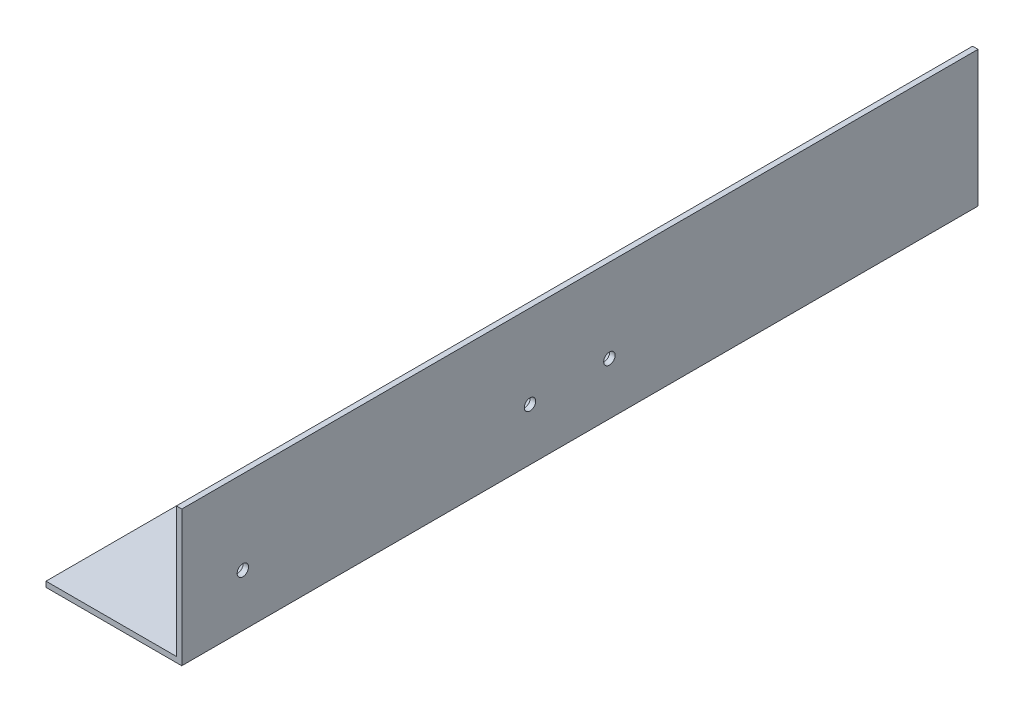
SolidWorks part; units mm, degrees
ref_plane "Front Plane" through (0, 0, 0) normal (0, 0, 1) x (1, 0, 0)
ref_plane "Top Plane" through (0, 0, 0) normal (0, 1, 0) x (1, 0, 0)
ref_plane "Right Plane" through (0, 0, 0) normal (1, 0, 0) x (0, 0, -1)
sketch "Sketch1" plane through (0, 0, 0) normal (0, 0, 1) x (1, 0, 0)
  line L0 (0, 0) -> (-50, 0)
  line L1 (-50, 0) -> (-50, 2)
  line L2 (-50, 2) -> (-2, 2)
  line L3 (-2, 2) -> (-2, 50)
  line L4 (-2, 50) -> (0, 50)
  line L5 (0, 50) -> (0, 0)
  dimension "D1" = 50
  dimension "D2" = 50
  dimension "D3" = 2
  dimension "D4" = 2
extrude "Boss-Extrude1" add sketch "Sketch1" along normal blind 293.25
sketch "Sketch2" plane through (0, 0, 0) normal (1, 0, 0) x (0, 0, -1)
  circle A0 centre (-135.75, 19.25) radius 2.1
  circle A1 centre (-165, 19.25) radius 2.1
  circle A2 centre (-270.75, 19.25) radius 2.1
  dimension "D1" = 4.2
  dimension "D2" = 19.25
  dimension "D3" = 135.75
  dimension "D4" = 165
  dimension "D5" = 270.75
extrude "Cut-Extrude1" cut sketch "Sketch2" against normal mid plane 10
sketch "Sketch3" plane through (0, 0, 0) normal (0, 1, 0) x (1, 0, 0)
  circle A0 centre (-25, -12.5) radius 2.75
  circle A1 centre (-25, -37.5) radius 2.75
  dimension "D1" = 5.5
  dimension "D2" = 25
  dimension "D3" = 12.5
  dimension "D4" = 37.5
extrude "Cut-Extrude2" cut sketch "Sketch3" against normal mid plane 10
